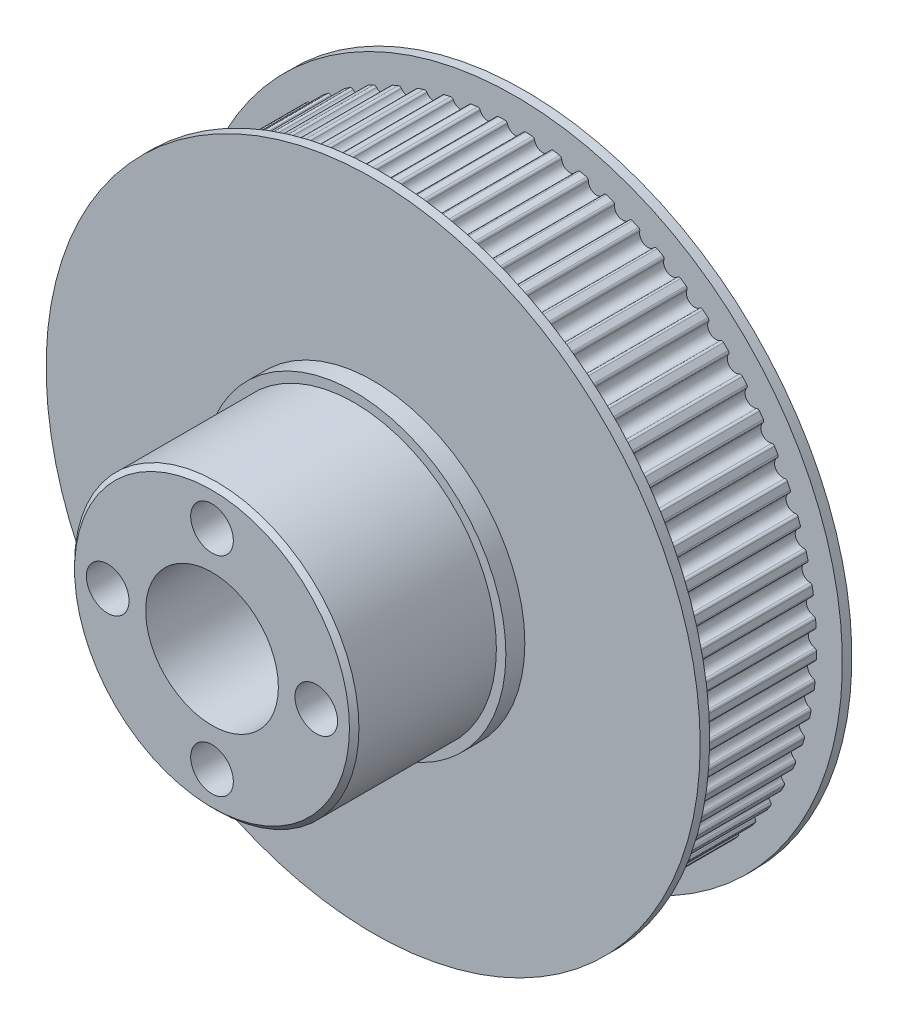
SolidWorks part; units mm, degrees
material "PLA+"
ref_plane "Front Plane" through (0, 0, 0) normal (0, 0, 1) x (1, 0, 0)
ref_plane "Top Plane" through (0, 0, 0) normal (0, 1, 0) x (1, 0, 0)
ref_plane "Right Plane" through (0, 0, 0) normal (1, 0, 0) x (0, 0, -1)
sketch "Sketch1" plane through (0, 0, 0) normal (0, 0, 1) x (1, 0, 0)
  circle A0 centre (0, 0) radius 32.9451 construction
  circle A1 centre (0, 0) radius 31.7751
  dimension "D1" = 65.8901
  dimension "D2" = 1.17
extrude "Boss-Extrude1" add sketch "Sketch1" along normal mid plane 15
sketch "Sketch2" plane through (0, 0, 7.5) normal (0, 0, 1) x (1, 0, 0)
  line L0 (0, 0) -> (0, 31.7751) construction
  circle A0 centre (0, 0) radius 31.7751 construction
  circle A1 centre (0, 31.7751) radius 0.87 construction
  circle A2 centre (-1.095, 31.496) radius 0.26 construction
  circle A3 centre (0, 0) radius 31.7751 construction
  arc A4 (-1.104, 31.7559) -> (-0.8431, 31.5602) centre (-1.095, 31.496) cw
  arc A5 (-0.8431, 31.5602) -> (0.8431, 31.5602) centre (0, 31.7751) ccw
  arc A6 (1.104, 31.7559) -> (0.8431, 31.5602) centre (1.095, 31.496) ccw
  arc A7 (-1.104, 31.7559) -> (1.104, 31.7559) centre (0, 0) cw
  dimension "D1" = 1.74
  dimension "D2" = 0.52
extrude "Cut-Extrude1" cut sketch "Sketch2" against normal through all both and the other way through all
pattern_circular "CirPattern1" count 69 over 360 about axis through (0, 0, 7.5) along (0, 0, -1) of "Cut-Extrude1"
sketch "Sketch7" plane through (0, 0, 7.5) normal (0, 0, 1) x (1, 0, 0)
  circle A0 centre (0, 0) radius 15
  point P16 (0, 0)
  dimension "D1" = 30
extrude "Boss-Extrude4" add sketch "Sketch7" along normal blind 17
sketch "Sketch8" plane through (0, 0, 7.5) normal (0, 0, 1) x (1, 0, 0)
  circle A0 centre (0, 0) radius 16
  dimension "D1" = 32
extrude "Boss-Extrude5" add sketch "Sketch8" along normal blind 2
sketch "Sketch9" plane through (0, 0, 24.5) normal (0, 0, 1) x (1, 0, 0)
  circle A0 centre (0, 0) radius 7
  circle A1 centre (0, 0) radius 11 construction
  circle A2 centre (0, -11) radius 2.25
  circle A3 centre (-11, 0) radius 2.25
  circle A4 centre (0, 11) radius 2.25
  circle A5 centre (11, 0) radius 2.25
  point P15 (0, 0)
  dimension "D1" = 14
  dimension "D2" = 22
  dimension "D3" = 4.5
  dimension "D4" = 4
extrude "Cut-Extrude2" cut sketch "Sketch9" against normal through all
sketch "Sketch10" plane through (0, 0, -7.5) normal (0, 0, -1) x (-1, 0, 0)
  circle A0 centre (11, 0) radius 3.6
  dimension "D1" = 7.2
extrude "Cut-Extrude3" cut sketch "Sketch10" against normal blind 5
pattern_circular "CirPattern2" count 4 over 360 about axis through (0, 0, -7.5) along (0, 0, 1) of "Cut-Extrude3" reverse direction yes
chamfer "Chamfer1" distance 0.5 angle 45 1 edges at (15, 0, 24.5)
sketch "Sketch11" plane through (0, 0, -7.5) normal (0, 0, -1) x (-1, 0, 0)
  circle A0 centre (0, 0) radius 34.5
  circle A1 centre (0, 0) radius 7
  circle A2 centre (11, 0) radius 2.25
  circle A3 centre (0, 11) radius 2.25
  circle A4 centre (-11, 0) radius 2.25
  circle A5 centre (0, -11) radius 2.25
  circle A6 centre (0, 11) radius 3.6
  circle A7 centre (11, 0) radius 3.6
  circle A8 centre (-11, 0) radius 3.6
  circle A9 centre (0, -11) radius 3.6
  dimension "D1" = 69
sketch "Sketch14" plane through (0, 0, 7.5) normal (0, 0, 1) x (1, 0, 0)
  circle A0 centre (0, 0) radius 34.5
  dimension "D1" = 69
extrude "Boss-Extrude7" add sketch "Sketch14" against normal blind 1
extrude "Boss-Extrude8" add sketch "Sketch11" along normal blind 1 contours A0 A9 A8 A7 A6 A1 region at (33.5242, 0, -7.5)
sketch "Sketch17" plane through (0, 0, -8.5) normal (0, 0, -1) x (-1, 0, 0)
  circle A0 centre (0, 11) radius 2.25
  circle A1 centre (11, 0) radius 2.25
  circle A2 centre (-11, 0) radius 2.25
  circle A3 centre (0, -11) radius 2.25
extrude "Cut-Extrude4" cut sketch "Sketch17" against normal through all
sketch "Sketch18" plane through (0, 0, -8.5) normal (0, 0, -1) x (-1, 0, 0)
  circle A0 centre (0, 0) radius 7
extrude "Cut-Extrude5" cut sketch "Sketch18" against normal through all
equation "\"ๅ\"=1"
